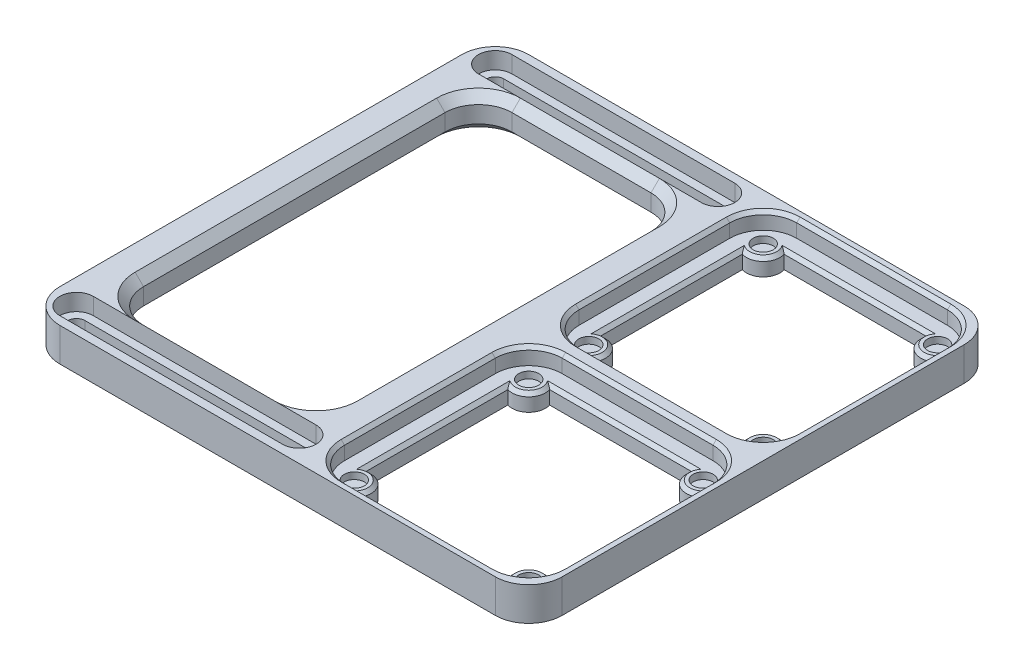
SolidWorks part; units mm, degrees
ref_plane "Front Plane" through (0, 0, 0) normal (0, 0, 1) x (1, 0, 0)
ref_plane "Top Plane" through (0, 0, 0) normal (0, 1, 0) x (1, 0, 0)
ref_plane "Right Plane" through (0, 0, 0) normal (1, 0, 0) x (0, 0, -1)
sketch "Sketch1" plane through (0, 0, 0) normal (0, 1, 0) x (1, 0, 0)
  line L1 (0, 0) -> (70, 0)
  line L2 (0, 0) -> (0, 70)
  line L3 (0, 70) -> (70, 70)
  line L4 (70, 0) -> (70, 70)
  dimension "D1" = 70
  dimension "D2" = 70
extrude "Boss-Extrude2" add sketch "Sketch1" along normal blind 7
sketch "Sketch3" plane through (0, 7, 0) normal (0, 1, 0) x (1, 0, 0)
  line L8 (2.5, 67.5) -> (2.5, 2.5)
  line L9 (2.5, 2.5) -> (67.5, 2.5)
  line L10 (67.5, 2.5) -> (67.5, 67.5)
  line L11 (67.5, 67.5) -> (2.5, 67.5)
  line L12 (2.5, 57.5) -> (2.5, 12.5)
  line L13 (12.5, 2.5) -> (57.5, 2.5)
  line L14 (67.5, 12.5) -> (67.5, 57.5)
  line L15 (57.5, 67.5) -> (12.5, 67.5)
  arc A0 (2.5, 12.5) -> (12.5, 2.5) centre (12.5, 12.5) ccw
  arc A1 (57.5, 2.5) -> (67.5, 12.5) centre (57.5, 12.5) ccw
  arc A2 (67.5, 57.5) -> (57.5, 67.5) centre (57.5, 57.5) ccw
  arc A3 (2.5, 57.5) -> (12.5, 67.5) centre (12.5, 57.5) cw
  dimension "D2" = 10
  dimension "D1" = 2.5
extrude "Cut-Extrude1" cut sketch "Sketch3" against normal blind 5
sketch "Sketch9" plane through (0, 0, 0) normal (0, -1, 0) x (1, 0, 0)
  line L1 (0, -70) -> (70, -70)
  line L2 (0, -70) -> (0, 0)
  line L3 (0, 0) -> (70, 0)
  line L4 (70, -70) -> (70, 0)
extrude "Boss-Extrude3" add sketch "Sketch9" along normal blind 5
sketch "Sketch20" plane through (0, 2, 0) normal (0, 1, 0) x (1, 0, 0)
  line L0 (35, 35) -> (8.9645, 61.0355) construction
  line L19 (12.5, 7.5) -> (57.5, 7.5)
  line L20 (62.5, 12.5) -> (62.5, 57.5)
  line L21 (57.5, 62.5) -> (12.5, 62.5)
  line L22 (7.5, 57.5) -> (7.5, 12.5)
  line L23 (13.7452, 7.5) -> (56.2548, 7.5)
  line L24 (62.5, 13.7452) -> (62.5, 56.2548)
  line L25 (56.2548, 62.5) -> (13.7452, 62.5)
  line L26 (7.5, 56.2548) -> (7.5, 13.7452)
  arc A0 (56.2548, 62.5) -> (62.5, 56.2548) centre (61.0355, 61.0355) ccw
  arc A1 (62.5, 13.7452) -> (56.2548, 7.5) centre (61.0355, 8.9645) ccw
  arc A2 (13.7452, 7.5) -> (7.5, 13.7452) centre (8.9645, 8.9645) ccw
  circle A4 centre (8.9645, 61.0355) radius 3
  circle A5 centre (8.9645, 8.9645) radius 3
  circle A6 centre (61.0355, 8.9645) radius 3
  circle A7 centre (61.0355, 61.0355) radius 3
  arc A21 (7.5, 56.2548) -> (13.7452, 62.5) centre (8.9645, 61.0355) ccw
  arc A24 (7.5, 12.5) -> (12.5, 7.5) centre (12.5, 12.5) ccw
  arc A25 (57.5, 7.5) -> (62.5, 12.5) centre (57.5, 12.5) ccw
  arc A26 (62.5, 57.5) -> (57.5, 62.5) centre (57.5, 57.5) ccw
  arc A27 (12.5, 62.5) -> (7.5, 57.5) centre (12.5, 57.5) ccw
  point P8 (35, 35)
  dimension "D2" = 6
  dimension "D3" = 4
  dimension "D4" = 36.8198
  dimension "D1" = 5
extrude "Cut-Extrude11" cut sketch "Sketch20" against normal through all contours L23 A1 L24 A0 L25 A21 L26 A2
sketch "Sketch21" plane through (0, 2, 0) normal (0, 1, 0) x (1, 0, 0)
  circle A0 centre (8.9645, 61.0355) radius 3
  circle A1 centre (61.0355, 61.0355) radius 3
  circle A2 centre (61.0355, 8.9645) radius 3
  circle A3 centre (8.9645, 8.9645) radius 3
extrude "Cut-Extrude12" cut sketch "Sketch21" against normal blind 2 contours A0 | A1 | A2 | A3
chamfer "Chamfer3" distance 1 angle 45 16 edges at (35, 7, -2.5) (64.5711, 7, -5.4289) (5.4289, 7, -5.4289) (67.5, 7, -35) (2.5, 7, -35) (64.5711, 7, -64.5711) (5.4289, 7, -64.5711) (35, 7, -67.5) (12.5, 2, -12.5) (35, 2, -7.5) (57.5, 2, -12.5) (62.5, 2, -35) (57.5, 2, -57.5) (7.5, 2, -35) (12.5, 2, -57.5) (35, 2, -62.5)
sketch "Sketch22" plane through (0, -5, 0) normal (0, -1, 0) x (1, 0, 0)
  line L0 (7.5, -13.7452) -> (7.5, -56.2548)
  line L1 (0, 0) -> (70, 0)
  line L2 (0, 0) -> (0, -70)
  line L3 (0, -70) -> (70, -70)
  line L4 (70, 0) -> (70, -70)
  line L6 (13.7452, -62.5) -> (56.2548, -62.5)
  line L8 (62.5, -56.2548) -> (62.5, -13.7452)
  line L10 (56.2548, -7.5) -> (13.7452, -7.5)
  arc A0 (7.5, -13.7452) -> (13.7452, -7.5) centre (8.9645, -8.9645) ccw
  arc A1 (56.2548, -7.5) -> (62.5, -13.7452) centre (61.0355, -8.9645) ccw
  arc A2 (62.5, -56.2548) -> (56.2548, -62.5) centre (61.0355, -61.0355) ccw
  arc A3 (13.7452, -62.5) -> (7.5, -56.2548) centre (8.9645, -61.0355) ccw
extrude "Cut-Extrude13" cut sketch "Sketch22" against normal blind 2
ref_plane "Plane2" through (0, 0, -35) normal (0, 0, 1) x (1, 0, 0)
ref_plane "Plane3" through (35, 0, 0) normal (-1, 0, 0) x (0, 0, 1)
mirror "Mirror2" about plane through (0, 7, -70) normal (0, 0, 1) of bodies 117 126
ref_plane "Plane6" through (0, 0, -70) normal (0, 0, 1) x (1, 0, 0)
fillet "Fillet1" radius 10 2 edges at (70, 2, 0) (70, 2, -140)
sketch "Sketch23" plane through (0, 0, 0) normal (-1, 0, 0) x (0, 0, 1)
  line L1 (-140, 7) -> (0, 7)
  line L2 (-140, 7) -> (-140, -3)
  line L3 (-140, -3) -> (0, -3)
  line L4 (0, 7) -> (0, -3)
extrude "Boss-Extrude4" add sketch "Sketch23" along normal blind 80
sketch "Sketch24" plane through (0, 7, 0) normal (0, 1, 0) x (1, 0, 0)
  line L1 (-72.5, 7.5) -> (-6, 7.5) construction
  line L2 (-72.5, 5) -> (-6, 5)
  line L4 (-72.5, 10) -> (-6, 10)
  line L9 (-72.5, 132.5) -> (-6, 132.5) construction
  line L14 (-72.5, 135) -> (-6, 135)
  line L15 (-72.5, 130) -> (-6, 130)
  arc A0 (-72.5, 135) -> (-72.5, 130) centre (-72.5, 132.5) ccw
  arc A1 (-6, 130) -> (-6, 135) centre (-6, 132.5) ccw
  arc A2 (-72.5, 5) -> (-72.5, 10) centre (-72.5, 7.5) cw
  arc A3 (-6, 10) -> (-6, 5) centre (-6, 7.5) cw
  point P6 (-39.25, 7.5)
  point P8 (-39.25, 132.5)
extrude "Cut-Extrude14" cut sketch "Sketch24" against normal blind 70 contours A3 L4 A2 L2 | L15 A1 L14 A0 region at (-39.25, 7, -7.5) region at (-39.25, 7, -132.5)
fillet "Fillet2" radius 10 2 edges at (-80, 2, 0) (-80, 2, -140)
sketch "Sketch25" plane through (0, 7, 0) normal (0, 1, 0) x (1, 0, 0)
  line L2 (-75, 10) -> (-75, 130)
  line L3 (-75, 10) -> (-75, 130)
  line L4 (-75, 130) -> (-3.5, 130)
  line L5 (-3.5, 130) -> (-3.5, 10)
  line L6 (-3.5, 10) -> (-75, 10)
  line L7 (-70, 25) -> (-70, 115)
  line L8 (-60, 125) -> (-18.5, 125)
  line L9 (-8.5, 115) -> (-8.5, 25)
  line L10 (-18.5, 15) -> (-60, 15)
  line L11 (-8.5, 125) -> (-8.5, 15) construction
  line L12 (-8.5, 15) -> (-70, 15) construction
  line L13 (-70, 15) -> (-70, 125) construction
  line L14 (-70, 125) -> (-8.5, 125) construction
  arc A0 (-8.5, 25) -> (-18.5, 15) centre (-18.5, 25) cw
  arc A1 (-70, 25) -> (-60, 15) centre (-60, 25) ccw
  arc A2 (-18.5, 125) -> (-8.5, 115) centre (-18.5, 115) cw
  arc A3 (-70, 115) -> (-60, 125) centre (-60, 115) cw
  dimension "D3" = 10
  dimension "D2" = 5
  dimension "D1" = 5
extrude "Cut-Extrude15" cut sketch "Sketch25" against normal blind 70 contours A3 L8 A2 L9 A0 L10 A1 L7
chamfer "Chamfer5" distance 2.5 angle 45 24 edges at (-39.25, 7, -5) (-75, 7, -7.5) (-3.5, 7, -7.5) (-39.25, 7, -10) (-39.25, 7, -130) (-75, 7, -132.5) (-3.5, 7, -132.5) (-39.25, 7, -135) (-39.25, -3, -15) (-11.4289, -3, -17.9289) (-67.0711, -3, -17.9289) (-8.5, -3, -70) (-70, -3, -70) (-11.4289, -3, -122.0711) (-67.0711, -3, -122.0711) (-39.25, -3, -125) (-11.4289, 7, -17.9289) (-39.25, 7, -15) (-8.5, 7, -70) (-67.0711, 7, -17.9289) (-11.4289, 7, -122.0711) (-70, 7, -70) (-39.25, 7, -125) (-67.0711, 7, -122.0711)
sketch "Sketch26" plane through (0, 7, 0) normal (0, 1, 0) x (1, 0, 0)
  line L150 (-72.5, 127.5) -> (-6, 127.5)
  line L151 (-6, 127.5) -> (-6, 137.5)
  line L152 (-6, 137.5) -> (-72.5, 137.5)
  arc A88 (-6, 127.5) -> (-6, 137.5) centre (-6, 132.5) ccw construction
  circle A89 centre (-72.5, 132.5) radius 5
  circle A90 centre (-6, 132.5) radius 5
  line M12 (-60, 127.5) -> (-72.5, 127.5)
  arc M13 (-72.5, 127.5) -> (-72.5, 137.5) centre (-72.5, 132.5) cw
  line M14 (-72.5, 137.5) -> (-6, 137.5)
  arc M15 (-6, 137.5) -> (-6, 127.5) centre (-6, 132.5) cw
  line M16 (-6, 127.5) -> (-18.5, 127.5)
extrude "Cut-Extrude16" cut sketch "Sketch26" against normal blind 5 contours A89 M13 | A90 A89 L150 M14 M12 M16 | L151 M15 | L151 A90 region at (-39.25, 7, -132.5) region at (-72.5, 7, -132.5) region at (-3.8779, 7, -132.5) region at (-8.1221, 7, -132.5)
sketch "Sketch27" plane through (0, 7, 0) normal (0, 1, 0) x (1, 0, 0)
  line L0 (-72.5, 12.5) -> (-6, 12.5)
  line L1 (-6, 12.5) -> (-6, 2.5)
  line L2 (-6, 2.5) -> (-72.5, 2.5)
  circle A0 centre (-72.5, 7.5) radius 5
  circle A1 centre (-6, 7.5) radius 5
  line M4 (-18.5, 12.5) -> (-6, 12.5)
  arc M5 (-6, 12.5) -> (-6, 2.5) centre (-6, 7.5) cw
  line M6 (-6, 2.5) -> (-72.5, 2.5)
  arc M7 (-72.5, 2.5) -> (-72.5, 12.5) centre (-72.5, 7.5) cw
  line M8 (-72.5, 12.5) -> (-60, 12.5)
extrude "Cut-Extrude17" cut sketch "Sketch27" against normal blind 5 contours L1 A1 | L1 M5 | A1 L0 A0 M4 M8 M6 | A0 M7 region at (-39.25, 7, -7.5) region at (-72.5, 7, -7.5) region at (-8.1221, 7, -7.5) region at (-3.8779, 7, -7.5)
